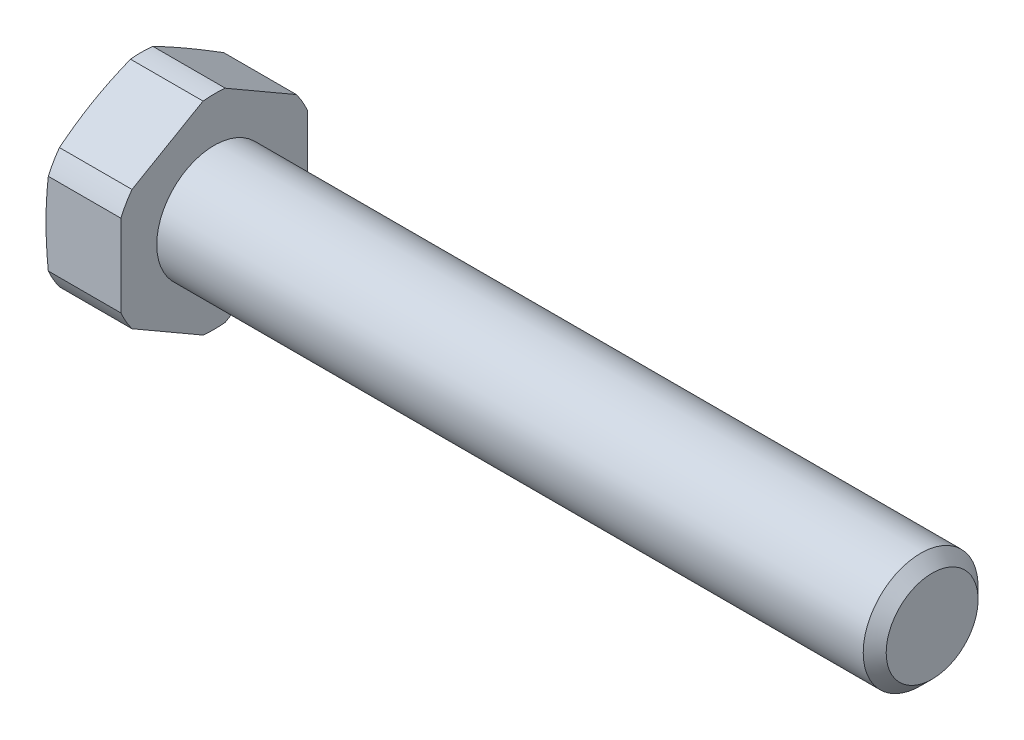
SolidWorks part; units mm, degrees
material "AISI 1020"
ref_plane "Спереди" through (0, 0, 0) normal (0, 0, 1) x (1, 0, 0)
ref_plane "Сверху" through (0, 0, 0) normal (0, 1, 0) x (1, 0, 0)
ref_plane "Справа" through (0, 0, 0) normal (1, 0, 0) x (0, 0, -1)
sketch "Эскиз1" plane through (0, 0, 0) normal (0, 0, 1) x (1, 0, 0)
  line L0 (-1000, 0) -> (49000, 0) construction
  line L1 (-5.3, 0) -> (-5.3, 6.175)
  line L2 (-5.3, 6.175) -> (-5.0521, 7.1)
  line L3 (-5.0521, 7.1) -> (0, 7.1)
  line L4 (0, 7.1) -> (0, 4)
  line L5 (0, 4) -> (49.2, 4)
  line L6 (50, 3.2) -> (50, 0)
  line L7 (50, 4) -> (50.625, 5.0825) construction
  line L8 (50.625, 5.0825) -> (51.25, 4) construction
  line L9 (51.25, 4) -> (50, 4) construction
  line L10 (50.625, 5.0825) -> (50.625, 4) construction
  line L11 (50.625, 5.0825) -> (28.625, 5.0825) construction
  line L12 (49.2, 4) -> (50, 3.2)
  line L13 (50, 4) -> (49.6, 3.6) construction
  line L14 (-5.3, 6.175) -> (-18.3, 6.175) construction
  line L15 (-5.3, 0) -> (50, 0)
  dimension "D1" = 0.8
  dimension "D2" = 15
revolve "Повернуть1" add sketch "Эскиз1" angle 360 about L0
cosmetic thread "Условное изображение резьбы1" parameters "D1"=22, "D2"=5.8349
sketch "Эскиз2" plane through (-5.3, 0, 0) normal (-1, 0, 0) x (0, 0, 1)
  line L1 (0, 7.5056) -> (-6.5, 3.7528)
  line L2 (-6.5, 3.7528) -> (-6.5, -3.7528)
  line L3 (-6.5, -3.7528) -> (0, -7.5056)
  line L4 (0, -7.5056) -> (6.5, -3.7528)
  line L5 (6.5, -3.7528) -> (6.5, 3.7528)
  line L6 (6.5, 3.7528) -> (0, 7.5056)
  circle A0 centre (0, 0) radius 6.5 construction
  dimension "D1" = 13
extrude "Вырез-Вытянуть1" cut sketch "Эскиз2" against normal up to surface (55.3 mm away) flip side to cut up to face at (50, 0, 3.2)
equation "\"D1@Эскиз1\"=\"_d_@Эскиз1\"/10"
equation "\"D@Эскиз1\"=\"S_@Эскиз1\"*0.95"
equation "\"D1@Эскиз2\"=\"S_@Эскиз1\""
equation "\"D1@Условное изображение резьбы1\"=\"b_@Эскиз1\""
equation "\"D2@Условное изображение резьбы1\"=\"_d_@Эскиз1\"-\"dr@Эскиз1\"*2"
